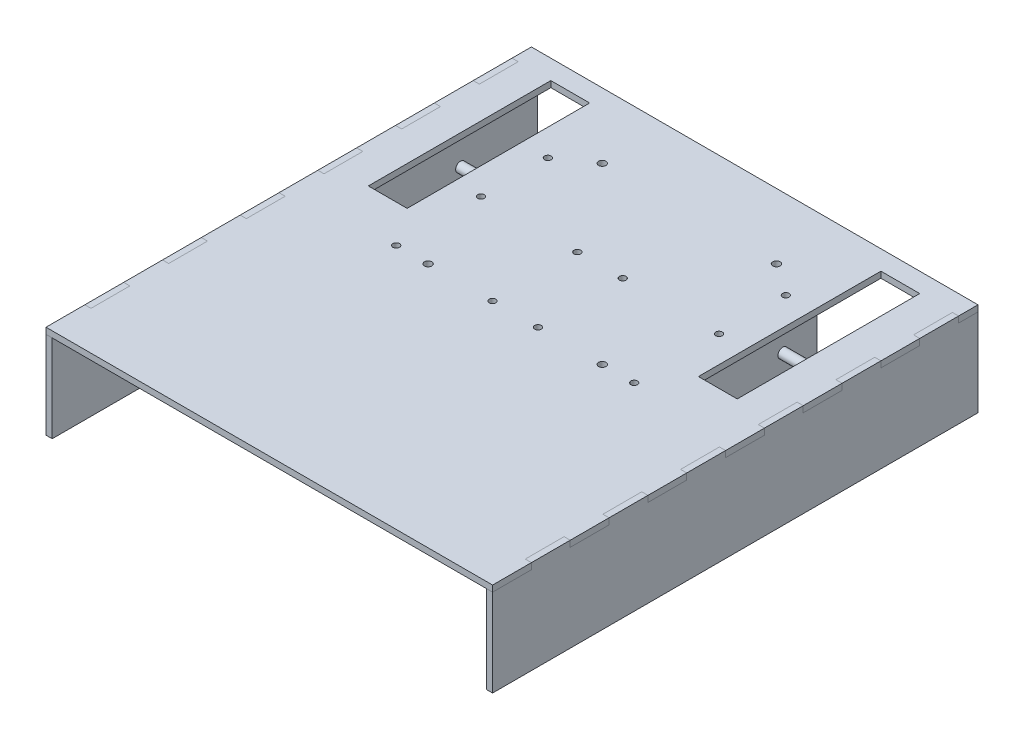
SolidWorks part; units mm, degrees
ref_plane "Front Plane" through (0, 0, 0) normal (0, 0, 1) x (1, 0, 0)
ref_plane "Top Plane" through (0, 0, 0) normal (0, 1, 0) x (1, 0, 0)
ref_plane "Right Plane" through (0, 0, 0) normal (1, 0, 0) x (0, 0, -1)
sketch "Sketch2" plane through (0, 0, 0) normal (0, 1, 0) x (1, 0, 0)
  line L7 (-172.2662, -88.2141) -> (57.7338, -88.2141)
  line L8 (17.7338, 151.7859) -> (37.7338, 151.7859)
  line L9 (57.7338, -88.2141) -> (57.7338, -68.2141)
  line L10 (57.7338, -68.2141) -> (54.5588, -68.2141)
  line L11 (54.5588, -68.2141) -> (54.5588, -48.2141)
  line L12 (54.5588, -48.2141) -> (57.7338, -48.2141)
  line L13 (-172.2662, -88.2141) -> (-172.2662, -68.2141)
  line L14 (-172.2662, -68.2141) -> (-169.0912, -68.2141)
  line L15 (-169.0912, -68.2141) -> (-169.0912, -48.2141)
  line L16 (-169.0912, -48.2141) -> (-172.2662, -48.2141)
  line L17 (-172.2662, -48.2141) -> (-172.2662, -28.2141)
  line L18 (-172.2662, -28.2141) -> (-169.0912, -28.2141)
  line L19 (-169.0912, -28.2141) -> (-169.0912, -8.2141)
  line L20 (-169.0912, -8.2141) -> (-172.2662, -8.2141)
  line L21 (57.7338, -28.2141) -> (54.5588, -28.2141)
  line L22 (54.5588, -28.2141) -> (54.5588, -8.2141)
  line L23 (54.5588, -8.2141) -> (57.7338, -8.2141)
  line L24 (57.7338, -48.2141) -> (57.7338, -28.2141)
  line L25 (-172.2662, -8.2141) -> (-172.2662, 11.7859)
  line L26 (-172.2662, 11.7859) -> (-169.0912, 11.7859)
  line L27 (-169.0912, 11.7859) -> (-169.0912, 31.7859)
  line L28 (-169.0912, 31.7859) -> (-172.2662, 31.7859)
  line L29 (57.7338, 11.7859) -> (54.5588, 11.7859)
  line L30 (54.5588, 11.7859) -> (54.5588, 31.7859)
  line L31 (54.5588, 31.7859) -> (57.7338, 31.7859)
  line L32 (57.7338, -8.2141) -> (57.7338, 11.7859)
  line L33 (-172.2662, 31.7859) -> (-172.2662, 51.7859)
  line L34 (-172.2662, 51.7859) -> (-169.0912, 51.7859)
  line L35 (-169.0912, 51.7859) -> (-169.0912, 71.7859)
  line L36 (-169.0912, 71.7859) -> (-172.2662, 71.7859)
  line L37 (57.7338, 51.7859) -> (54.5588, 51.7859)
  line L38 (54.5588, 51.7859) -> (54.5588, 71.7859)
  line L39 (54.5588, 71.7859) -> (57.7338, 71.7859)
  line L40 (57.7338, 31.7859) -> (57.7338, 51.7859)
  line L45 (17.7338, 151.7859) -> (17.7338, 57.7859)
  line L46 (17.7338, 57.7859) -> (37.7338, 57.7859)
  line L47 (37.7338, 151.7859) -> (37.7338, 57.7859)
  line L48 (-152.2662, 151.7859) -> (-132.2662, 151.7859)
  line L49 (-152.2662, 151.7859) -> (-152.2662, 57.7859)
  line L50 (-152.2662, 57.7859) -> (-132.2662, 57.7859)
  line L51 (-132.2662, 151.7859) -> (-132.2662, 57.7859)
  line L52 (-172.2662, 71.7859) -> (-172.2662, 91.7859)
  line L53 (-172.2662, 91.7859) -> (-169.0912, 91.7859)
  line L54 (-169.0912, 91.7859) -> (-169.0912, 111.7859)
  line L55 (-169.0912, 111.7859) -> (-172.2662, 111.7859)
  line L56 (57.7338, 91.7859) -> (54.5588, 91.7859)
  line L57 (54.5588, 91.7859) -> (54.5588, 111.7859)
  line L58 (54.5588, 111.7859) -> (57.7338, 111.7859)
  line L59 (57.7338, 71.7859) -> (57.7338, 91.7859)
  line L63 (-172.2662, 111.7859) -> (-172.2662, 131.7859)
  line L64 (-172.2662, 131.7859) -> (-169.0912, 131.7859)
  line L65 (-169.0912, 131.7859) -> (-169.0912, 151.7859)
  line L66 (-169.0912, 151.7859) -> (-172.2662, 151.7859)
  line L67 (57.7338, 131.7859) -> (54.5588, 131.7859)
  line L68 (54.5588, 131.7859) -> (54.5588, 151.7859)
  line L69 (54.5588, 151.7859) -> (57.7338, 151.7859)
  line L70 (57.7338, 111.7859) -> (57.7338, 131.7859)
  line L71 (57.7338, 151.7859) -> (57.7338, 161.7859)
  line L72 (57.7338, 161.7859) -> (-172.2662, 161.7859)
  line L73 (-172.2662, 161.7859) -> (-172.2662, 151.7859)
  dimension "D1" = 3.175
  dimension "D2" = 20
  dimension "D3" = 20
  dimension "D4" = 3.175
  dimension "D6" = 230
  dimension "D8" = 20
  dimension "D9" = 20
  dimension "D10" = 20
  dimension "D11" = 20
  dimension "D13" = 94
  dimension "D7" = 10
  dimension "D12" = 10
  dimension "D5" = 6
extrude "Boss-Extrude1" add sketch "Sketch2" along normal blind 3.175
ref_plane "Plane3" through (-57.2662, 0, 0) normal (-1, 0, 0) x (0, 0, 1)
sketch "Sketch3" plane through (-169.0912, 0, 0) normal (-1, 0, 0) x (0, 0, 1)
  line L0 (68.2141, 3.175) -> (68.2141, 0)
  line L1 (68.2141, 0) -> (88.2141, 0)
  line L2 (88.2141, 0) -> (88.2141, -45)
  line L3 (68.2141, 3.175) -> (48.2141, 3.175)
  line L4 (48.2141, 3.175) -> (48.2141, 0)
  line L5 (48.2141, 0) -> (28.2141, 0)
  line L6 (28.2141, 0) -> (28.2141, 3.175)
  line L7 (28.2141, 3.175) -> (8.2141, 3.175)
  line L8 (8.2141, 3.175) -> (8.2141, 0)
  line L9 (8.2141, 0) -> (-11.7859, 0)
  line L10 (-11.7859, 0) -> (-11.7859, 3.175)
  line L11 (-91.7859, 0) -> (-91.7859, 3.175)
  line L12 (-11.7859, 3.175) -> (-31.7859, 3.175)
  line L13 (-31.7859, 3.175) -> (-31.7859, 0)
  line L14 (-31.7859, 0) -> (-51.7859, 0)
  line L15 (-51.7859, 0) -> (-51.7859, 3.175)
  line L16 (-51.7859, 3.175) -> (-71.7859, 3.175)
  line L17 (-71.7859, 3.175) -> (-71.7859, 0)
  line L18 (-71.7859, 0) -> (-91.7859, 0)
  line L21 (-91.7859, 3.175) -> (-111.7859, 3.175)
  line L22 (-111.7859, 3.175) -> (-111.7859, 0)
  line L25 (-111.7859, 0) -> (-131.7859, 0)
  line L26 (-151.7859, 0) -> (-131.7859, 0) construction
  line L27 (-131.7859, 3.175) -> (-131.7859, 0) construction
  line L28 (-131.7859, 0) -> (-131.7859, 3.175)
  line L29 (-131.7859, 3.175) -> (-151.7859, 3.175)
  line L30 (-151.7859, 3.175) -> (-151.7859, 0)
  line L31 (-151.7859, 3.175) -> (-151.7859, 0) construction
  line L32 (-151.7859, 0) -> (-161.732, 0)
  line L33 (-161.732, 0) -> (-161.732, -45)
  line L34 (-161.732, -45) -> (88.2141, -45)
extrude "Boss-Extrude2" add sketch "Sketch3" along normal blind 3.175 separate body
sketch "Sketch4" plane through (0, 0, 0) normal (0, -1, 0) x (1, 0, 0)
  line L0 (-128.2662, -122.8126) -> (-128.2662, -33.5103)
  line L1 (-128.2662, -122.8126) -> (-110.4256, -122.8126)
  line L2 (-128.2662, -33.5103) -> (-110.4287, -33.5103)
  line L5 (-64.765, -32.9867) -> (-64.765, -87.1773)
  line L6 (-64.765, -32.9867) -> (-73.1795, -32.9867)
  line L7 (-64.765, -87.1773) -> (-73.1795, -87.1773)
  line L9 (-110.4287, -33.5103) -> (-110.4287, -55.4044)
  line L10 (-110.4287, -55.4044) -> (-73.1795, -55.4044)
  line L11 (-73.1795, -55.4044) -> (-73.1795, -32.9867)
  line L12 (-73.1795, -87.1773) -> (-73.1795, -65.4044)
  line L13 (-73.1795, -65.4044) -> (-110.4256, -65.4044)
  line L14 (-110.4256, -65.4044) -> (-110.4256, -122.8126)
extrude "Boss-Extrude3" add sketch "Sketch4" along normal blind 1.6129 separate body
sketch "Sketch6" plane through (-128.2662, 113.8349, 0) normal (1, 0, 0) x (0, -1, 0)
  line L0 (115.4478, 33.5103) -> (113.8349, 33.5103)
  line L1 (113.8349, 33.5103) -> (113.8349, 122.8126)
  line L4 (133.4041, 33.5103) -> (115.4478, 33.5103)
  line L7 (135.755, 122.8126) -> (113.8349, 122.8126)
  line L8 (113.8349, 57.7859) -> (113.8349, 151.7859) construction
  line L10 (115.4478, 122.8126) -> (113.8349, 122.8126) construction
  line L11 (135.755, 122.8126) -> (135.755, 87.3557)
  circle A2 centre (133.4041, 73.86) radius 1.27
  circle A4 centre (133.4041, 51.6858) radius 2.3749
  circle A5 centre (125.8349, 105.2548) radius 2.55
  circle A6 centre (123.1933, 51.6858) radius 1.27
  circle A8 centre (143.6149, 51.6858) radius 1.27
  arc A10 (135.755, 87.3557) -> (133.4041, 33.5103) centre (121.4093, 61.008) cw
  line M25 (113.8349, 33.5103) -> (113.8349, 122.8126)
  line M26 (113.8349, 122.8126) -> (115.4478, 122.8126)
  line M27 (115.4478, 122.8126) -> (115.4478, 33.5103)
  line M28 (115.4478, 33.5103) -> (113.8349, 33.5103)
  dimension "D1" = 5.1
  dimension "D2" = 12
extrude "Boss-Extrude4" add sketch "Sketch6" along normal blind 1.6129 contours M28 M25 M26 M27 | L4 M27 | A6 A2 A4 A8 region at (-128.2662, -15.7988, -73.9814) region at (-128.2662, -0.8065, -78.1615)
sketch "Sketch7" plane through (0, -1.6129, 0) normal (0, -1, 0) x (1, 0, 0)
  circle A0 centre (-118.541, -82.125) radius 1.7
  circle A1 centre (-118.541, -38.4299) radius 1.7
  circle A2 centre (-68.9723, -38.4299) radius 1.7
  circle A3 centre (-68.9723, -82.125) radius 1.7
  circle A4 centre (-118.541, -116.5476) radius 1.7
  circle A5 centre (-102.1184, -38.4299) radius 1.9
  circle A6 centre (-102.1184, -128.1299) radius 1.9
  dimension "D3" = 3.4
  dimension "D4" = 3.4
  dimension "D5" = 3.4
  dimension "D6" = 3.4
  dimension "D1" = 3.4
  dimension "D2" = 3.8
  dimension "D8" = 3.8
  dimension "D7" = 89.7
extrude "Cut-Extrude1" cut sketch "Sketch7" against normal blind 10
mirror "Mirror1" about plane through (-57.2662, 0, 0) normal (-1, 0, 0) of bodies 157 103 158
mirror "Mirror2" about plane through (-57.2662, 0, 0) normal (-1, 0, 0) of "Cut-Extrude1"
sketch "Sketch9" plane through (-152.2662, 0, 0) normal (1, 0, 0) x (0, 0, -1)
  circle A0 centre (105.2548, -12) radius 2.5
extrude "Boss-Extrude6" add sketch "Sketch9" along normal blind 189 separate body
equation "\"hardboard_width\"= 3.175"
equation "\"D1@Boss-Extrude1\"=\"hardboard_width\""
equation "\"D1@Sketch2\"=\"hardboard_width\""
equation "\"D4@Sketch2\"=\"hardboard_width\""
equation "\"D1@Boss-Extrude2\"=\"hardboard_width\""
equation "\"steel_24g_thickness\"= 0.5"
equation "\"m3_clearance_hole\"= 3.4"
equation "\"D3@Sketch7\"=\"m3_clearance_hole\""
equation "\"D4@Sketch7\"=\"m3_clearance_hole\""
equation "\"D5@Sketch7\"=\"m3_clearance_hole\""
equation "\"D6@Sketch7\"=\"m3_clearance_hole\""
equation "\"steel_16g_thickness\"=1.6129"
equation "\"D1@Boss-Extrude3\"=\"steel_16g_thickness\""
equation "\"D1@Boss-Extrude4\"=\"steel_16g_thickness\""
equation "\"D1@Sketch7\"=\"m3_clearance_hole\""
